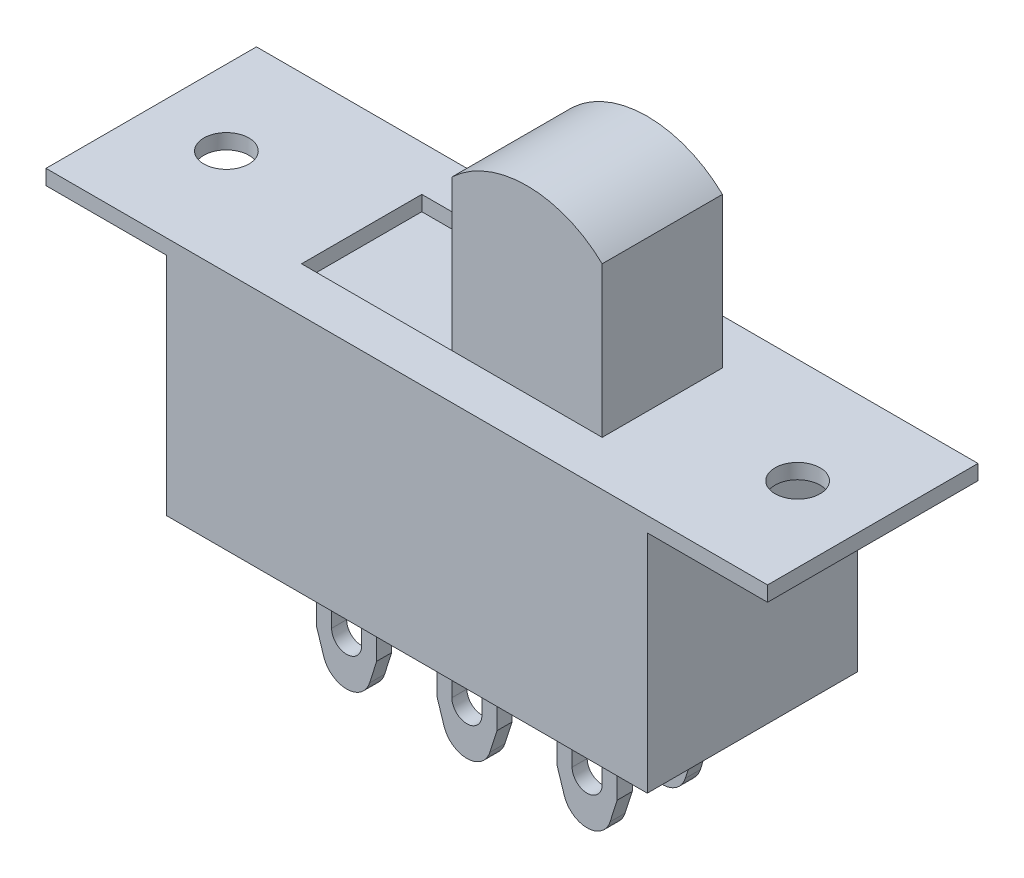
SolidWorks part; units mm, degrees
material "ABS"
ref_plane "Ebene vorne" through (0, 0, 0) normal (0, 0, 1) x (1, 0, 0)
ref_plane "Ebene oben" through (0, 0, 0) normal (0, 1, 0) x (1, 0, 0)
ref_plane "Ebene rechts" through (0, 0, 0) normal (1, 0, 0) x (0, 0, -1)
sketch "Skizze1" plane through (0, 0, 0) normal (0, 0, 1) x (1, 0, 0)
  line L0 (-12, 8) -> (12, 8)
  line L1 (12, 8) -> (12, 7.5)
  line L2 (12, 7.5) -> (8, 7.5)
  line L3 (8, 7.5) -> (8, 0)
  line L4 (8, 0) -> (-8, 0)
  line L5 (0, -9.4678) -> (0, 14.715) construction
  line L6 (-8, 7.5) -> (-8, 0)
  line L7 (-12, 7.5) -> (-8, 7.5)
  line L8 (-12, 8) -> (-12, 7.5)
  line L9 (0, 8) -> (0, 13)
  line L10 (5, 13) -> (5, 8)
  arc A0 (0, 13) -> (5, 13) centre (2.5, 10.375) cw
  point P10 (0, 0)
  point P13 (0, 8)
  point P18 (2.5, 14)
  dimension "D1" = 16
  dimension "D2" = 8
  dimension "D3" = 0.5
  dimension "D4" = 24
  dimension "D5" = 1
  dimension "D6" = 6
  dimension "D7" = 5
  dimension "D8" = 7
extrude "Aufsatz-Linear austragen1" add sketch "Skizze1" along normal mid plane 7 contours L5 L4 L3 L2 L1 L0 | L4 L5 L0 L8 L7 L6 region at (-4.1818, 4.1136, 0) region at (4.1818, 4.1136, 0)
extrude "Aufsatz-Linear austragen2" add sketch "Skizze1<3>" along normal mid plane 4 contours A0 L9 L0 L10 region at (2.5, 10.8512, 0)
sketch "Skizze1<3>" plane through (0, 0, 0) normal (0, 0, 1) x (1, 0, 0) same geometry as "Skizze1"
sketch "Skizze2" plane through (0, 0, 3.5) normal (0, 0, 1) x (1, 0, 0)
  line L0 (-5, 0) -> (-5, -2.7)
  line L1 (8, 0) -> (-8, 0) construction
  line L2 (-5, -2.7) -> (-4.7619, -3.4439)
  line L3 (-3.2381, -3.4439) -> (-3, -2.7)
  line L4 (-3, -2.7) -> (-3, 0)
  line L5 (-3, 0) -> (-5, 0)
  line L6 (-4, 0) -> (-4, -3.2) construction
  line L7 (-4, -1.5) -> (-4, -2.5) construction
  line L8 (-3.5, -1.5) -> (-3.5, -2.5)
  line L9 (-4.5, -1.5) -> (-4.5, -2.5)
  arc A0 (-4.7619, -3.4439) -> (-3.2381, -3.4439) centre (-4, -3.2) ccw
  arc A1 (-3.5, -1.5) -> (-4.5, -1.5) centre (-4, -1.5) ccw
  arc A2 (-4.5, -2.5) -> (-3.5, -2.5) centre (-4, -2.5) ccw
  point P12 (-4, -2)
  point P17 (-4, -4)
  dimension "D1" = 4
  dimension "D4" = 0.8
  dimension "D6" = 0.5
  dimension "D2" = 2
  dimension "D3" = 2.7
  dimension "D5" = 1
  dimension "D7" = 2
  dimension "D8" = 4
extrude "Aufsatz-Linear austragen3" add sketch "Skizze2" against normal blind 0.5 from offset 2 separate body offset against normal yes
pattern_linear "Lineares Muster1" count 3 spacing 4 along (1, 0, 0) count 2 spacing 2.5 along (0, 0, -1) of "Aufsatz-Linear austragen3"
sketch "Skizze3" plane through (0, 8, 0) normal (0, 1, 0) x (1, 0, 0)
  line L0 (-9.5, 0) -> (9.5, 0) construction
  circle A0 centre (-9.5, 0) radius 0.75
  circle A1 centre (9.5, 0) radius 0.75
  dimension "D1" = 1.5
  dimension "D2" = 19
extrude "Schnitt-Linear austragen1" cut sketch "Skizze3" against normal through all
sketch "Skizze4" plane through (0, 8, 0) normal (0, 1, 0) x (1, 0, 0)
  line L0 (0, -2) -> (5, -2) construction
  line L1 (-5, 2) -> (0, 2)
  line L2 (0, 2) -> (0, -2)
  line L3 (0, -2) -> (-5, -2)
  line L4 (-5, 2) -> (-5, -2)
extrude "Schnitt-Linear austragen2" cut sketch "Skizze4" against normal blind 0.5
